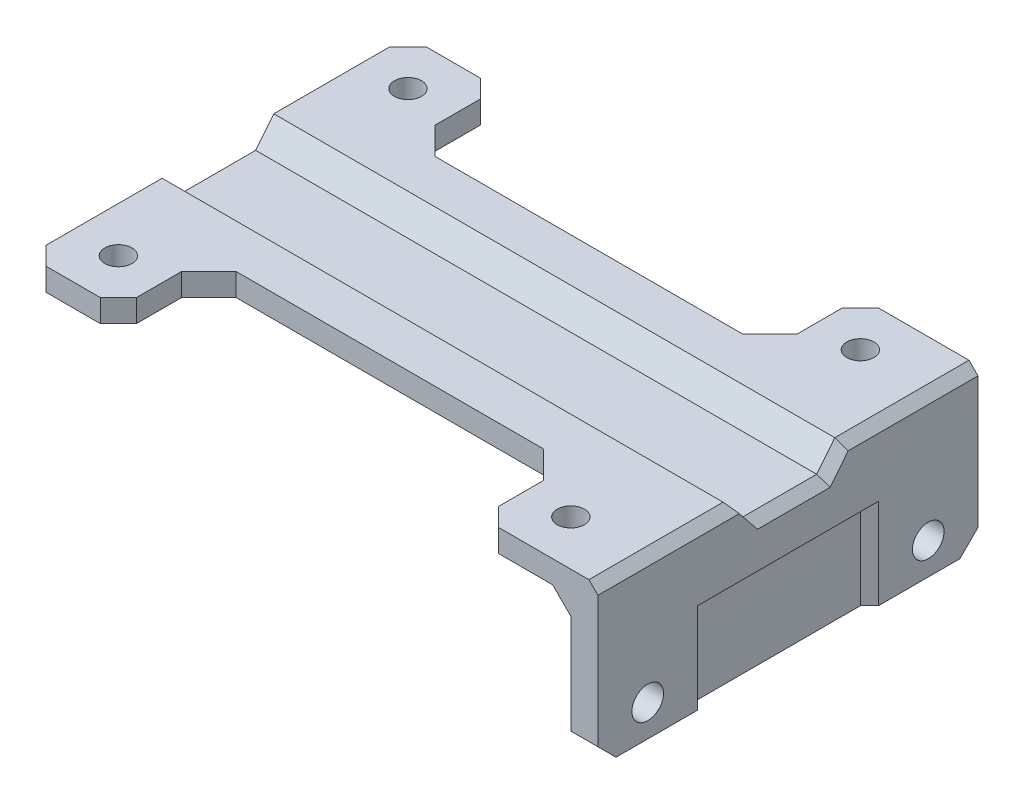
SolidWorks part; units mm, degrees
material "9400A光敏树脂"
ref_plane "前视基准面" through (0, 0, 0) normal (0, 0, 1) x (1, 0, 0)
ref_plane "上视基准面" through (0, 0, 0) normal (0, 1, 0) x (1, 0, 0)
ref_plane "右视基准面" through (0, 0, 0) normal (1, 0, 0) x (0, 0, -1)
other "Configuration Table"
sketch "草图2" plane through (0, 0, 0) normal (0, 1, 0) x (1, 0, 0)
  line L1 (-30, -21) -> (30, -21)
  line L2 (-30, -21) -> (-30, 21)
  line L3 (-30, 21) -> (30, 21)
  line L4 (30, -21) -> (30, 21)
  line L5 (-30, -21) -> (30, 21) construction
  line L6 (-30, 21) -> (30, -21) construction
  point P0 (0, 0)
  dimension "D1" = 60
  dimension "D2" = 42
extrude "凸台-拉伸1" add sketch "草图2" along normal blind 2.5
sketch "草图3" plane through (0, 0, 0) normal (0, 1, 0) x (1, 0, 0)
  line L0 (30, -21) -> (30, 21) construction
  line L1 (-25, -16) -> (25, -16) construction
  line L2 (-25, -16) -> (-25, 16) construction
  line L3 (-25, 16) -> (25, 16) construction
  line L4 (25, -16) -> (25, 16) construction
  line L5 (-25, -16) -> (25, 16) construction
  line L6 (-25, 16) -> (25, -16) construction
  line L7 (-30, -21) -> (30, -21) construction
  circle A0 centre (-25, 16) radius 1.5
  circle A1 centre (25, 16) radius 1.5
  circle A2 centre (-25, -16) radius 1.5
  circle A3 centre (25, -16) radius 1.5
  point P0 (0, 0)
  dimension "D3" = 3
  dimension "D4" = 3
  dimension "D5" = 3
  dimension "D6" = 3
  dimension "D1" = 50
  dimension "D2" = 32
extrude "切除-拉伸1" cut sketch "草图3" against normal up to surface (2.5 mm away) from surface at 2.5 up to face at (0, 0, 0) starting at face at (0, 2.5, 0)
sketch "草图6" plane through (0, 0, 0) normal (0, 1, 0) x (1, 0, 0)
  line L0 (-30, -21) -> (30, -21) construction
  line L1 (-30, 21) -> (-20, 21) construction
  line L2 (-30, 21) -> (-30, -21) construction
  line L3 (-30, -21) -> (-20, -21) construction
  line L4 (-20, 21) -> (-20, -21) construction
  line L6 (30, 21) -> (20, 21) construction
  line L7 (30, 21) -> (30, -21) construction
  line L8 (30, -21) -> (20, -21) construction
  line L9 (20, 21) -> (20, -21) construction
  line L10 (-30, 11) -> (30, 11) construction
  line L11 (-30, 11) -> (-30, -11) construction
  line L12 (-30, -11) -> (30, -11) construction
  line L13 (30, 11) -> (30, -11) construction
  line L14 (-20, 21) -> (20, 21)
  line L15 (-20, 21) -> (-20, 11)
  line L16 (-20, 11) -> (20, 11)
  line L17 (20, 21) -> (20, 11)
  line L18 (-20, -21) -> (20, -21)
  line L19 (-20, -21) -> (-20, -11)
  line L20 (-20, -11) -> (20, -11)
  line L21 (20, -21) -> (20, -11)
  point P16 (-30, 0)
  dimension "D1" = 10
  dimension "D2" = 10
  dimension "D3" = 22
extrude "切除-拉伸2" cut sketch "草图6" along normal up to surface (2.5 mm away) from surface at 0 up to face at (25, 2.5, -17.5) starting at face at (25, 0, -17.5)
sketch "草图7" plane through (0, 0, 0) normal (0, 1, 0) x (1, 0, 0)
  line L0 (-30, 21) -> (-30, -21) construction
  line L1 (-30, 5) -> (30, 5)
  line L2 (-30, 5) -> (-30, -5)
  line L3 (-30, -5) -> (30, -5)
  line L4 (30, 5) -> (30, -5)
  line L5 (30, -21) -> (30, 21) construction
  point P8 (30, 0)
  dimension "D1" = 10
extrude "凸台-拉伸3" add sketch "草图7" against normal blind 6 from surface at 0 starting at face at (25, 0, -17.5)
sketch "草图9" plane through (0, 0, 0) normal (0, 1, 0) x (1, 0, 0)
  line L1 (30, 21) -> (33, 21)
  line L2 (30, 21) -> (30, -21)
  line L3 (30, -21) -> (33, -21)
  line L4 (33, 21) -> (33, -21)
  dimension "D1" = 3
  dimension "D2" = 42
extrude "凸台-拉伸4" add sketch "草图9" against normal blind 17.5 from surface at 2.5 starting at face at (25, 2.5, -17.5)
sketch "草图11" plane through (0, 0, 0) normal (1, 0, 0) x (0, 0, -1)
  line L0 (5, -6) -> (11, 0)
  line L2 (5, 0) -> (21, 0) construction
  line L3 (11, 0) -> (5, 0)
  line L4 (5, 0) -> (5, -6)
  line L5 (21, 2.5) -> (21, 0) construction
  line L6 (-5, -6) -> (-5, 0)
  line L7 (-5, 0) -> (-11, 0)
  line L8 (-5, 0) -> (-21, 0) construction
  line L9 (-11, 0) -> (-5, -6)
  dimension "D1" = 10
  dimension "D2" = 10
extrude "凸台-拉伸5" add sketch "草图11" against normal up to surface (60 mm away) from surface at 30 up to face at (-30, -0.875, 0) starting at face at (30, -5.25, 0)
sketch "草图16" plane through (0, 0, 0) normal (1, 0, 0) x (0, 0, -1)
  line L0 (21, -15) -> (21, 2.5) construction
  line L1 (-21, -15) -> (21, -15) construction
  line L2 (-21, -15) -> (-21, -6) construction
  line L3 (-21, -6) -> (21, -6) construction
  line L4 (21, -15) -> (21, -6) construction
  line L5 (-15.5, -11.5) -> (15.5, -11.5) construction
  circle A0 centre (15.5, -11.5) radius 3.5 construction
  circle A1 centre (-15.5, -11.5) radius 3.5 construction
  circle A2 centre (-15.5, -11.5) radius 1.75
  circle A3 centre (15.5, -11.5) radius 1.75
  point P10 (0, -11.5)
  dimension "D4" = 3.5
  dimension "D5" = 3.5
  dimension "D1" = 9
  dimension "D2" = 31
  dimension "D3" = 3.5
extrude "切除-拉伸3" cut sketch "草图16" against normal up to surface (3 mm away) from surface
sketch "草图18" plane through (0, 0, 0) normal (1, 0, 0) x (0, 0, -1)
  line L0 (11, 0) -> (5, -6) construction
  line L1 (11, 0) -> (21, 0) construction
  line L2 (5, -6) -> (-5, -6) construction
  line L3 (-5, -6) -> (-11, 0) construction
  line L4 (-11, 0) -> (11, 0) construction
  line L5 (6.1716, -2) -> (4.1716, -4)
  line L6 (4.1716, -4) -> (-4.1716, -4)
  line L7 (-4.1716, -4) -> (-6.1716, -2)
  line L8 (-6.1716, -2) -> (6.1716, -2)
  dimension "D1" = 2
extrude "切除-拉伸4" cut sketch "草图18" along normal up to surface (60 mm away) from surface
chamfer "倒角1" distance 2 angle 45 4 edges at (30, 0, 16) (30, -3, 8) (30, -3, -8) (30, 0, -16)
sketch "草图19" plane through (0, 0, 0) normal (1, 0, 0) x (0, 0, -1)
  line L0 (6.1716, 2.5) -> (4.1716, 0)
  line L1 (21, 2.5) -> (-21, 2.5) construction
  line L2 (4.1716, 0) -> (-4.1716, 0)
  line L3 (-4.1716, 0) -> (-6.1716, 2.5)
  line L4 (-6.1716, 2.5) -> (6.1716, 2.5)
  dimension "D1" = 2.5
extrude "切除-拉伸6" cut sketch "草图19" along normal up to surface (63 mm away) from surface at -30 up to face at (33, -11.5, 13.75) starting at face at (-30, -3, 0)
chamfer "倒角2" distance 2 angle 45 8 edges at (20, 1.25, -21) (20, 1.25, 21) (-20, 1.25, 21) (-30, 1.25, 21) (-20, 1.25, -21) (-30, 1.25, -21) (31.5, -15, 21) (31.5, -15, -21)
sketch "草图21" plane through (0, 0, 0) normal (1, 0, 0) x (0, 0, -1)
  line L0 (-19, -15) -> (19, -15) construction
  line L1 (-10, -5) -> (10, -5)
  line L2 (-10, -5) -> (-10, -15)
  line L3 (-10, -15) -> (10, -15)
  line L4 (10, -5) -> (10, -15)
  point P6 (0, -5)
  dimension "D1" = 20
  dimension "D2" = 10
extrude "切除-拉伸7" cut sketch "草图21" against normal blind 1 from surface at 33 starting at face at (33, -11.5, 13.75)
chamfer "倒角3" distance 1 angle 45 7 edges at (33, 2.5, 13.5858) (33, 0, 0) (33, 1.25, -5.1716) (33, 2.5, -13.5858) (32, -10, -10) (32, -10, 10) (32, -5, 0)
chamfer "倒角4" distance 3 angle 45 4 edges at (-20, 1.25, 11) (20, 1.25, 11) (20, 1.25, -11) (-20, 1.25, -11)
